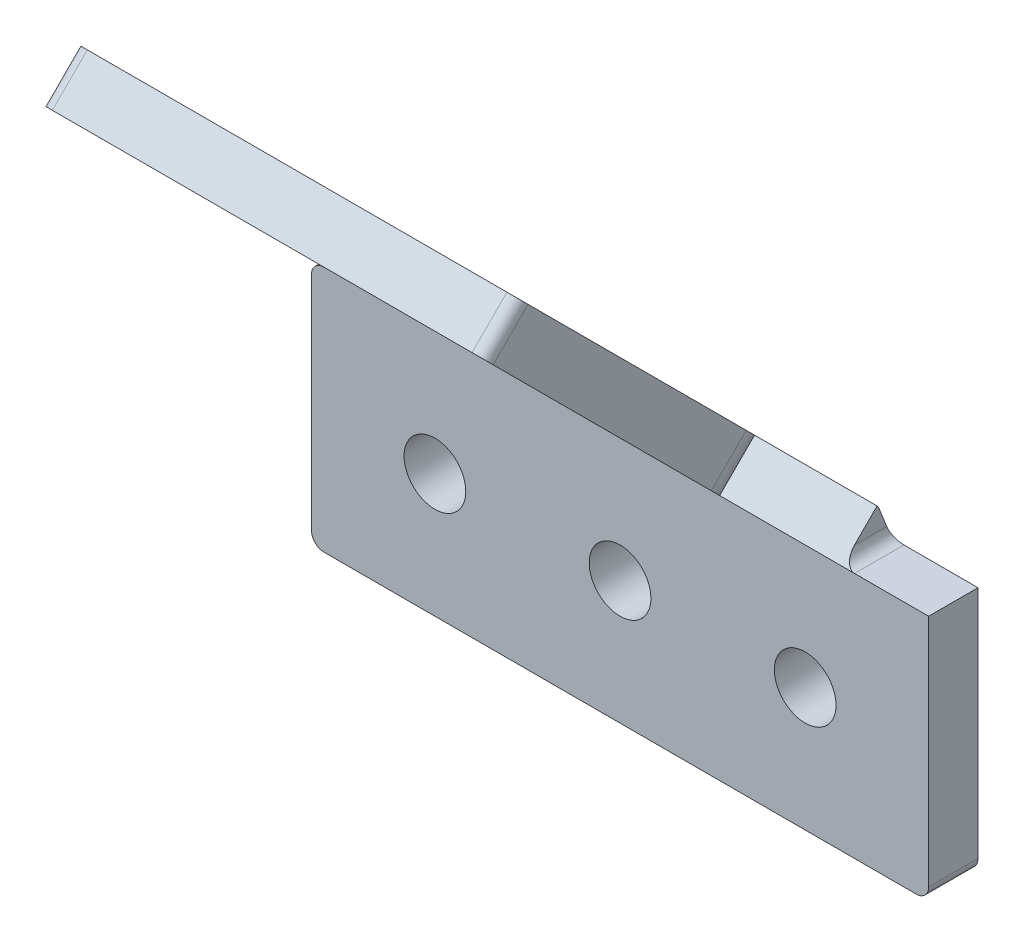
SolidWorks part; units mm, degrees
ref_plane "前视基准面" through (0, 0, 0) normal (0, 0, 1) x (1, 0, 0)
ref_plane "上视基准面" through (0, 0, 0) normal (0, 1, 0) x (1, 0, 0)
ref_plane "右视基准面" through (0, 0, 0) normal (1, 0, 0) x (0, 0, -1)
sketch "草图1" plane through (0, 0, 0) normal (0, 0, 1) x (1, 0, 0)
  line L1 (25, -10) -> (-25, -10)
  line L2 (25, -10) -> (25, 10)
  line L3 (25, 10) -> (-25, 10)
  line L4 (-25, -10) -> (-25, 10)
  line L5 (25, -10) -> (-25, 10) construction
  line L6 (25, 10) -> (-25, -10) construction
  point P0 (0, 0)
  dimension "D1" = 20
  dimension "D2" = 50
extrude "凸台-拉伸1" add sketch "草图1" along normal blind 4
sketch "草图4" plane through (0, 0, 0) normal (1, 0, 0) x (0, 0, -1)
  line L0 (-4, 10) -> (-32.9914, 38.9914)
  line L1 (-32.9914, 38.9914) -> (-30.163, 41.8198)
  line L2 (-30.163, 41.8198) -> (-1.0879, 12.7448)
  line L3 (-1.0879, 12.7448) -> (0, 10)
  line L4 (-4, 10) -> (0, 10)
  line L5 (-4, -10) -> (-4, 10) construction
  line L6 (-4, 10) -> (0, 10) construction
  line L7 (0, -10) -> (0, 10) construction
  point P11 (0, 0)
  point P12 (0, 0)
  point P14 (0, 0)
  point P16 (0, 0)
  dimension "D1" = 135
  dimension "D2" = 41
  dimension "D3" = 4
  dimension "D4" = 45
extrude "凸台-拉伸2" add sketch "草图4" along normal mid plane 36
sketch "草图5" plane through (0, 3, -3) normal (0, -0.7071, 0.7071) x (1, 0, 0)
  line L0 (18, 50.8995) -> (-18, 9.8995) construction
  circle A2 centre (12.7216, 44.888) radius 1.5
  circle A3 centre (-13.6705, 14.8304) radius 1.5
  dimension "D1" = 8
  dimension "D2" = 3
  dimension "D3" = 3
  dimension "D4" = 40
extrude "切除-拉伸1" cut sketch "草图5" against normal through all contours A2 | A2 | A3 | A3 region at (12.7216, 34.7406, 28.7406) region at (-13.6705, 13.4867, 7.4867)
sketch "草图6" plane through (0, 3, -3) normal (0, -0.7071, 0.7071) x (1, 0, 0)
  line L1 (18, 9.8995) -> (3, 9.8995)
  line L2 (18, 9.8995) -> (18, 21.8995)
  line L3 (18, 21.8995) -> (3, 21.8995)
  line L4 (3, 9.8995) -> (3, 21.8995)
  dimension "D1" = 15
  dimension "D2" = 12
extrude "切除-拉伸2" cut sketch "草图6" against normal through all
fillet "圆角1" radius 1 2 edges at (3, 11.4142, 2.5858) (3, 19.8995, 11.0711)
fillet "圆角2" radius 1 7 edges at (25, -10, 2) (-25, -10, 2) (-18, 40.4056, 31.5772) (18, 40.4056, 31.5772) (-25, 10, 2) (-18, 10, 2) (18, 10, 2)
fillet "圆角3" radius 1 1 edges at (0, 12.7448, 1.0879)
sketch "草图7" plane through (0, 3, -3) normal (0, -0.7071, 0.7071) x (1, 0, 0)
  circle A0 centre (12.7216, 44.888) radius 2.5
  circle A1 centre (-13.6705, 14.8304) radius 2.5
  dimension "D1" = 5
  dimension "D2" = 5
extrude "切除-拉伸3" cut sketch "草图7" against normal blind 2
sketch "草图8" plane through (0, 0, 4) normal (0, 0, 1) x (1, 0, 0)
  line L0 (0, -10) -> (0, 0) construction
  line L1 (-24, -10) -> (24, -10) construction
  circle A0 centre (0, 0) radius 2.5
  circle A1 centre (15, 0) radius 2.5
  circle A2 centre (-15, 0) radius 2.5
  dimension "D1" = 5
  dimension "D2" = 10
  dimension "D3" = 2
  dimension "D4" = 2
extrude "切除-拉伸4" cut sketch "草图8" against normal through all
sketch "草图9" plane through (0, 3, -3) normal (0, -0.7071, 0.7071) x (1, 0, 0)
  line L1 (-11, 21.071) -> (-1, 21.071)
  line L2 (-11, 21.071) -> (-11, 17.1671)
  line L3 (-11, 17.1671) -> (-1, 17.1671)
  line L4 (-1, 21.071) -> (-1, 17.1671)
  line L5 (-0.7, 16.8671) -> (-11.3, 16.8671)
  line L6 (-0.7, 16.8671) -> (-0.7, 21.371)
  line L7 (-0.7, 21.371) -> (-11.3, 21.371)
  line L8 (-11.3, 16.8671) -> (-11.3, 21.371)
  line L9 (-0.7, 16.8671) -> (-11.3, 21.371) construction
  line L10 (-0.7, 21.371) -> (-11.3, 16.8671) construction
  point P6 (-6, 19.119)
  dimension "D1" = 0.3
  dimension "D2" = 0.3
  dimension "D3" = 0.3
  dimension "D4" = 0.3
extrude "切除-拉伸5" cut sketch "草图9" against normal blind 10 contours L7 L8 L5 L6
fillet "圆角4" radius 3 1 edges at (18, 19.8995, 11.0711)
